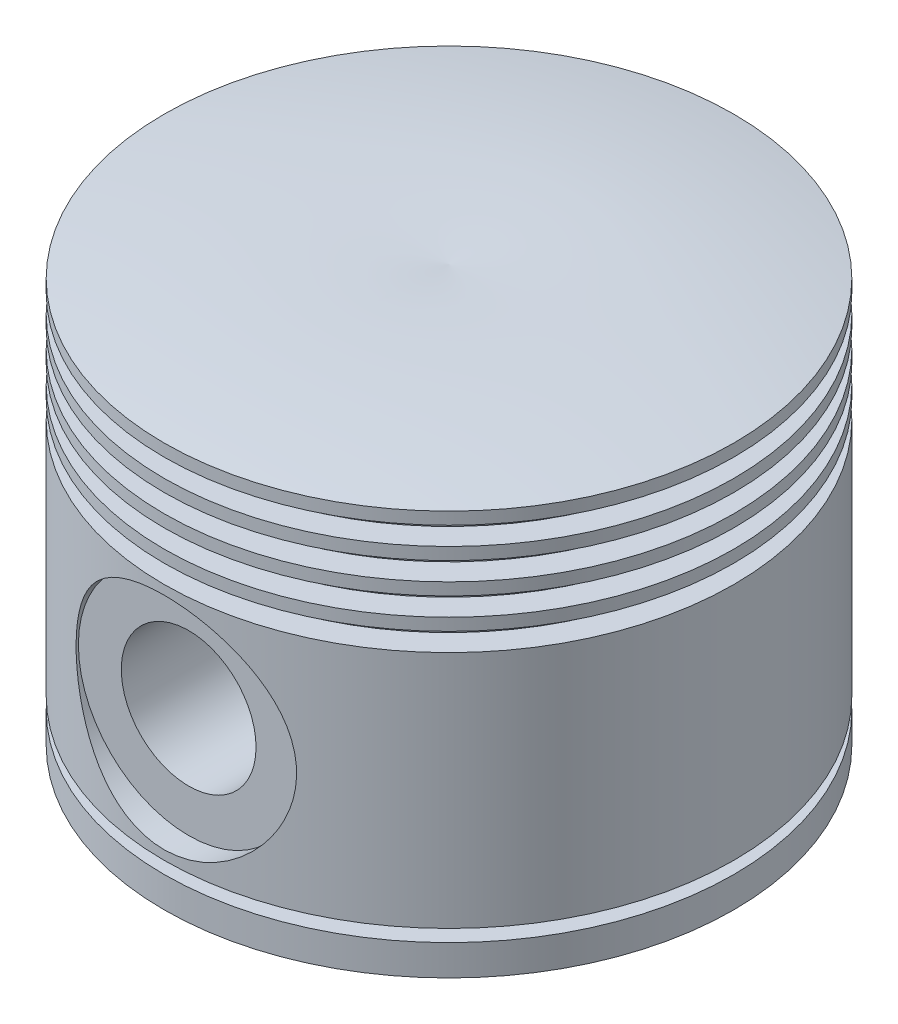
SolidWorks part; units mm, degrees
ref_plane "Front Plane" through (0, 0, 0) normal (0, 0, 1) x (1, 0, 0)
ref_plane "Top Plane" through (0, 0, 0) normal (0, 1, 0) x (1, 0, 0)
ref_plane "Right Plane" through (0, 0, 0) normal (1, 0, 0) x (0, 0, -1)
sketch "Sketch1" plane through (0, 0, 0) normal (1, 0, 0) x (0, 0, -1)
  line L0 (0, 54.443) -> (0, -13.557)
  line L1 (0, -13.557) -> (-42.5, -13.557)
  line L2 (-42.5, -13.557) -> (-46.5, -13.557)
  line L3 (-46.5, -13.557) -> (-46.5, -8.557)
  line L4 (-46.5, -8.557) -> (0, -8.557)
  line L5 (-42.5, -8.557) -> (-42.5, -6.557)
  line L6 (-42.5, -6.557) -> (0, -6.557)
  line L7 (-42.5, -6.557) -> (-46.5, -6.557)
  line L8 (-46.5, -6.557) -> (-46.5, 31.443)
  line L10 (-46.5, 31.443) -> (0, 31.443)
  line L11 (-46.5, 31.443) -> (-46.5, 32.443)
  line L12 (-46.5, 32.443) -> (0, 32.443)
  line L13 (-42.5, 32.443) -> (-42.5, 35.443)
  line L14 (-46.5, 35.443) -> (-42.5, 35.443)
  line L15 (-42.5, 35.443) -> (0, 35.443)
  line L16 (-46.5, 35.443) -> (-46.5, 37.443)
  line L17 (-46.5, 37.443) -> (0, 37.443)
  line L18 (-42.5, 37.443) -> (-42.5, 40.443)
  line L19 (-42.5, 40.443) -> (0, 40.443)
  line L20 (-46.5, 40.443) -> (-46.5, 42.443)
  line L21 (-46.5, 40.443) -> (-42.5, 40.443)
  line L22 (-46.5, 42.443) -> (0, 42.443)
  line L23 (-42.5, 42.443) -> (-42.5, 45.443)
  line L24 (-42.5, 45.443) -> (0, 45.443)
  line L25 (-46.5, 45.443) -> (-46.5, 47.443)
  line L26 (-46.5, 45.443) -> (-42.5, 45.443)
  line L27 (-46.5, 47.443) -> (0, 47.443)
  line L29 (-42.5, 47.443) -> (-42.5, 50.443)
  line L30 (-42.5, 50.443) -> (0, 50.443)
  line L31 (-46.5, 50.443) -> (-46.5, 52.443)
  line L32 (-46.5, 50.443) -> (-42.5, 50.443)
  line L33 (-46.5, 52.443) -> (0, 52.443)
  arc A0 (0, 54.443) -> (-46.5, 52.443) centre (-15.1903, -133.9456) ccw
  dimension "D16" = 189
  dimension "D1" = 42.5
  dimension "D2" = 4
  dimension "D3" = 5
  dimension "D4" = 2
  dimension "D5" = 38
  dimension "D6" = 1
  dimension "D7" = 3
  dimension "D8" = 2
  dimension "D9" = 3
  dimension "D10" = 2
  dimension "D11" = 3
  dimension "D12" = 2
  dimension "D13" = 3
  dimension "D14" = 2
  dimension "D15" = 2
revolve "Revolve1" add sketch "Sketch1" angle 360 about L0 region at (0, 53.5546, 19.3088) region at (0, 51.443, 23.25) region at (0, 48.943, 21.25) region at (0, 46.443, 23.25) region at (0, 43.943, 21.25) region at (0, 41.443, 23.25) region at (0, 38.943, 21.25) region at (0, 36.443, 23.25) region at (0, 33.943, 21.25) region at (0, 31.943, 23.25) region at (0, 12.443, 23.25) region at (0, -7.557, 21.25) region at (0, -11.057, 23.25)
sketch "Sketch3" plane through (0, -13.557, 0) normal (0, -1, 0) x (1, 0, 0)
  circle A0 centre (0, 0) radius 37
  dimension "D1" = 74
extrude "Cut-Extrude2" cut sketch "Sketch3" against normal blind 62 contours A0
sketch "Sketch5" plane through (0, 0, 0) normal (0, 0, 1) x (1, 0, 0)
  circle A0 centre (0, 12.943) radius 11
  circle A1 centre (0, 12.943) radius 18
  dimension "D1" = 36
  dimension "D2" = 22
extrude "Cut-Extrude3" cut sketch "Sketch5" along normal blind 10 from offset 42.5 contours A1
mirror "Mirror1" about plane through (0, 0, 0) normal (0, 0, 1) of "Cut-Extrude3"
extrude "Boss-Extrude1" add sketch "Sketch5<5>" along normal blind 15 from offset 25 contours A1
sketch "Sketch5<5>" plane through (0, 0, 0) normal (0, 0, 1) x (1, 0, 0) same geometry as "Sketch5"
mirror "Mirror2" about plane through (0, 0, 0) normal (0, 0, 1) of "Boss-Extrude1"
extrude "Cut-Extrude4" cut sketch "Sketch5<6>" against normal through all both and the other way through all contours A0 region at (0, 12.943, 0)
sketch "Sketch5<6>" plane through (0, 0, 0) normal (0, 0, 1) x (1, 0, 0) same geometry as "Sketch5"
